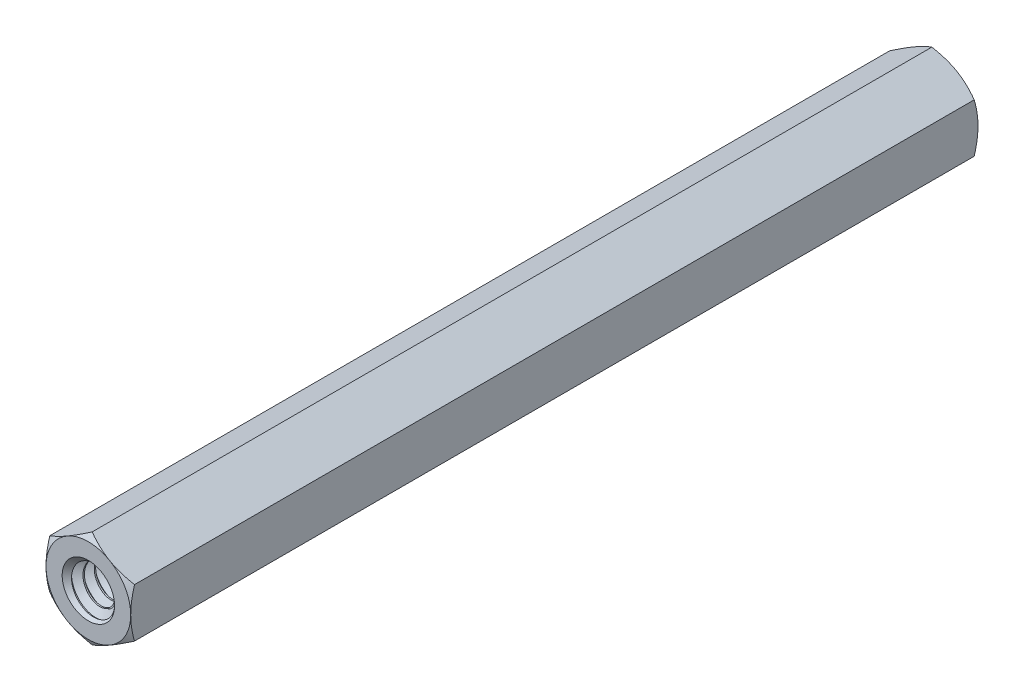
SolidWorks part; units mm, degrees
ref_plane "Front Plane" through (0, 0, 0) normal (0, 0, 1) x (1, 0, 0)
ref_plane "Top Plane" through (0, 0, 0) normal (0, 1, 0) x (1, 0, 0)
ref_plane "Right Plane" through (0, 0, 0) normal (1, 0, 0) x (0, 0, -1)
sketch "Sketch3" plane through (0, 0, 0) normal (1, 0, 0) x (0, 0, -1)
  line L0 (-23.8125, 0) -> (23.8125, 0) construction
  line L1 (0, 2.3813) -> (0, -2.3813) construction
  line L2 (-23.8125, 1.4224) -> (-23.8125, -1.4224) construction
  point P2 (17.4625, 0)
  point P3 (-17.4625, 0)
  dimension "Length" = 47.625
  dimension "Min Thread Length" = 6.35
  dimension "D1" = 6.35
  dimension "Thread Dia" = 2.8448
  dimension "Hex" = 4.7625
sketch "Sketch1" plane through (0, 0, 0) normal (0, 0, 1) x (1, 0, 0)
  line L1 (0, 2.7496) -> (-2.3812, 1.3748)
  line L2 (-2.3812, 1.3748) -> (-2.3812, -1.3748)
  line L3 (-2.3812, -1.3748) -> (0, -2.7496)
  line L4 (0, -2.7496) -> (2.3813, -1.3748)
  line L5 (2.3813, -1.3748) -> (2.3813, 1.3748)
  line L6 (2.3813, 1.3748) -> (0, 2.7496)
  circle A0 centre (0, 0) radius 2.3813 construction
  circle A1 centre (0, 0) radius 1.4224
extrude "Extrude1" add sketch "Sketch1" along normal up to vertex (23.8125 mm away) and the other way up to vertex (23.8125 mm away) up to point (0, 0, 23.8125) other way up to point (0, 0, -23.8125)
sketch "Sketch11" plane through (0, 0, -23.8125) normal (0, 0, -1) x (-1, 0, 0)
  circle A0 centre (0, 0) radius 1.4224 construction
  circle A1 centre (0, 0) radius 1.4224
curve "Helix/Spiral1" pitch 0.635 height 48.26 radius 1.4224 centre (0, 0, -23.8125) axis (0, 0, 1) start towards (0, 1, 0) parameters "Pitch"=0.635
sketch "Sketch12" plane through (0, 0, 0) normal (1, 0, 0) x (0, 0, -1)
  line L0 (24.3681, 1.4224) -> (23.8125, 1.4224)
  line L1 (24.3681, 1.4224) -> (24.13, 1.01)
  line L2 (24.13, 1.01) -> (24.0506, 1.01)
  line L3 (24.0506, 1.01) -> (23.8125, 1.4224)
  line L4 (24.0903, 1.01) -> (24.0903, 1.4224) construction
  line L5 (24.2491, 1.2162) -> (23.9316, 1.2162) construction
  dimension "D1" = 0.0794
  dimension "D2" = 0.3175
  dimension "D3" = 60
sweep "Sweep1" add profiles "Sketch12" path "Helix/Spiral1"
sketch "Sketch6" plane through (0, 0, -23.8125) normal (0, 0, -1) x (-1, 0, 0)
  line L6 (0, 2.7496) -> (-2.3813, 1.3748)
  line L7 (-2.3813, 1.3748) -> (-2.3813, -1.3748)
  line L8 (-2.3813, -1.3748) -> (0, -2.7496)
  line L9 (0, -2.7496) -> (2.3812, -1.3748)
  line L10 (2.3812, -1.3748) -> (2.3812, 1.3748)
  line L11 (2.3812, 1.3748) -> (0, 2.7496)
  line L12 (0, 2.7496) -> (-2.3813, 1.3748)
  line L13 (-2.3813, 1.3748) -> (-2.3813, -1.3748)
  line L14 (-2.3813, -1.3748) -> (0, -2.7496)
  line L15 (0, -2.7496) -> (2.3812, -1.3748)
  line L16 (2.3812, -1.3748) -> (2.3812, 1.3748)
  line L17 (2.3812, 1.3748) -> (0, 2.7496)
  dimension "D1" = 0
extrude "Extrude2" cut sketch "Sketch6" along normal through all
sketch "Sketch7" plane through (0, 0, -23.8125) normal (0, 0, -1) x (-1, 0, 0)
  circle A2 centre (0, 0) radius 1.4732
  circle A3 centre (0, 0) radius 1.4732
  dimension "D1" = 0.0508
extrude "Extrude3" cut sketch "Sketch7" against normal through all draft 43
sketch "Sketch8" plane through (0, 0, -23.8125) normal (0, 0, -1) x (-1, 0, 0)
  circle A0 centre (0, 0) radius 2.3813 construction
  circle A1 centre (0, 0) radius 2.3813
extrude "Extrude4" cut sketch "Sketch8" against normal through all draft 60 flip side to cut
mirror "Mirror1" about plane through (0, 0, 0) normal (0, 0, 1) of "Extrude2", "Extrude3", "Extrude4"
sketch "Sketch9" plane through (0, 0, 0) normal (1, 0, 0) x (0, 0, -1)
  line L1 (-17.4625, 1.4732) -> (17.4625, 1.4732)
  line L2 (-17.4625, 1.4732) -> (-17.4625, 0)
  line L3 (-17.4625, 0) -> (17.4625, 0)
  line L4 (17.4625, 1.4732) -> (17.4625, 0)
  line L7 (-23.8125, 0) -> (23.8125, 0) construction
revolve "Revolve" add sketch "Sketch9" angle 360 about L0
sketch "Sketch10" plane through (0, 0, 0) normal (1, 0, 0) x (0, 0, -1)
  line L0 (23.8125, 1.4224) -> (17.4625, 1.4224)
  line L1 (-23.8125, 1.4224) -> (-17.4625, 1.4224)
  line L2 (17.4625, 1.4224) -> (17.4625, -1.4224)
  line L3 (-23.8125, -1.4732) -> (-17.4625, -1.4732)
  line L4 (-17.4625, 1.4224) -> (-17.4625, -1.4732)
  line L5 (17.4625, -1.4224) -> (23.8125, -1.4224)
sketch "Sketch13" plane through (0, 0, 23.8125) normal (0, 0, 1) x (1, 0, 0)
  line L0 (0, 0) -> (1.01, 0) construction
  line L1 (0, 0) -> (0.7141, 0.7141) construction
  line L2 (0, 0) -> (0.7141, -0.7141) construction
  arc A0 (0.5533, -0.8449) -> (0.9908, -0.1958) centre (0, 0) ccw construction
  arc A1 (-0.7076, -0.7206) -> (0, -1.01) centre (0, 0) ccw construction
  dimension "D1" = 45
  dimension "D2" = 45
equation "\"D1@Sketch3\" = \"Min Thread Length@Sketch3\""
equation "\"D3@Helix/Spiral1\" = \"Length@Sketch3\"+\"Pitch@Helix/Spiral1\""
equation "\"D1@Sketch12\" = \"Pitch@Helix/Spiral1\"*.125"
equation "\"D2@Sketch12\" = \"Pitch@Helix/Spiral1\"*.5"
